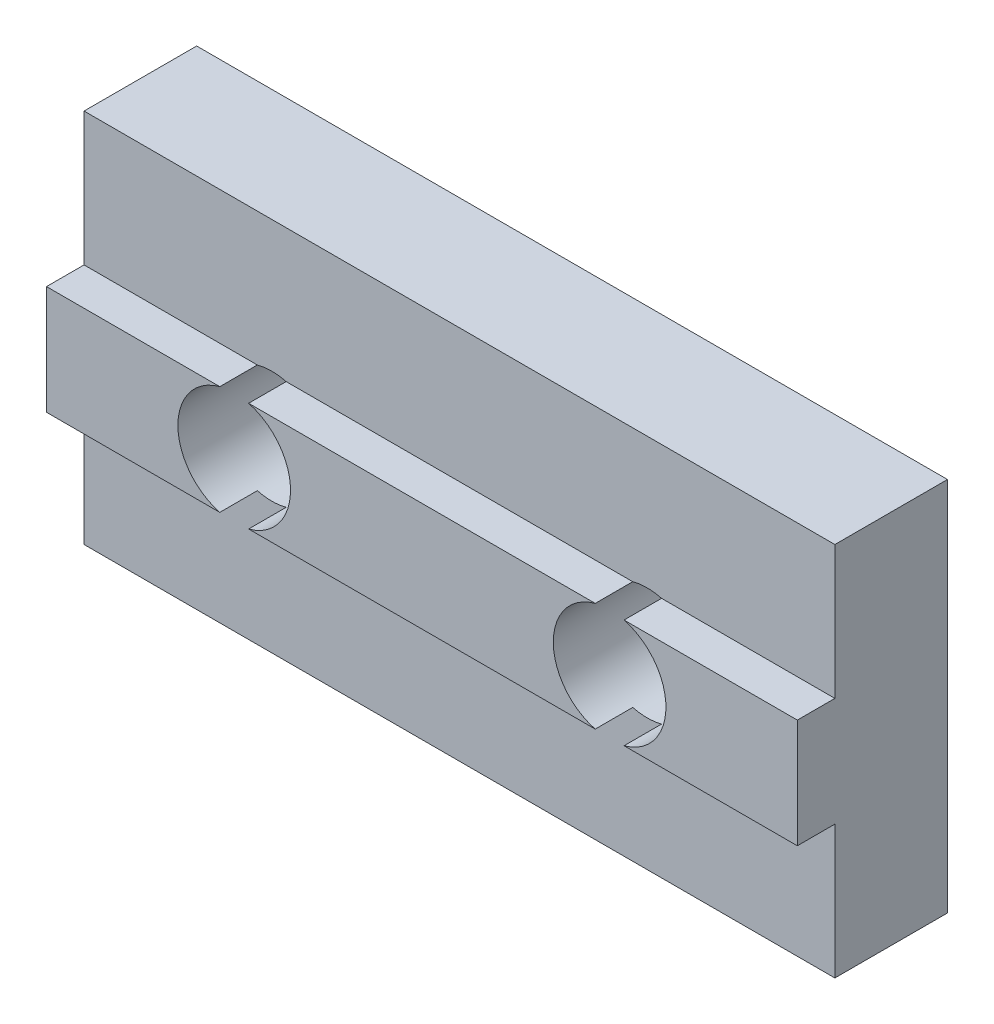
SolidWorks part; units mm, degrees
ref_plane "Front Plane" through (0, 0, 0) normal (0, 0, 1) x (1, 0, 0)
ref_plane "Top Plane" through (0, 0, 0) normal (0, 1, 0) x (1, 0, 0)
ref_plane "Right Plane" through (0, 0, 0) normal (1, 0, 0) x (0, 0, -1)
sketch "Esquisse1" plane through (0, 0, 0) normal (0, 0, 1) x (1, 0, 0)
  line L1 (0, 0) -> (20, 0)
  line L2 (0, 0) -> (0, 10)
  line L3 (0, 10) -> (20, 10)
  line L4 (20, 0) -> (20, 10)
  point P15 (0, 5)
  point P17 (20, 5)
  dimension "D1" = 20
  dimension "D2" = 10
extrude "Boss.-Extru.1" add sketch "Esquisse1" along normal blind 3
sketch "Esquisse2" plane through (0, 0, 3) normal (0, 0, 1) x (1, 0, 0)
  line L0 (20, 0) -> (20, 10) construction
  line L1 (20, 3.55) -> (0, 3.55)
  line L2 (20, 3.55) -> (20, 6.45)
  line L3 (20, 6.45) -> (0, 6.45)
  line L4 (0, 3.55) -> (0, 6.45)
  line L5 (0, 10) -> (0, 0) construction
  line L6 (0, 10) -> (0, 0) construction
  point P8 (0, 5)
  point P9 (0, 5)
  point P12 (0, 0)
  point P15 (0, 5)
  dimension "D1" = 2.9
extrude "Boss.-Extru.2" add sketch "Esquisse2" along normal blind 1
sketch "Esquisse3" plane through (0, 0, 0) normal (0, 0, -1) x (-1, 0, 0)
  line L0 (-20, 0) -> (-20, 10) construction
  circle A0 centre (-15, 5) radius 1.5
  point P2 (0, 0)
  point P5 (-20, 5)
  dimension "D1" = 3
  dimension "D2" = 5
extrude "Enlèv. mat.-Extru.1" cut sketch "Esquisse3" against normal through all
pattern_linear "Répétition linéaire1" count 2 spacing 10 along (-1, 0, 0) of "Enlèv. mat.-Extru.1"
